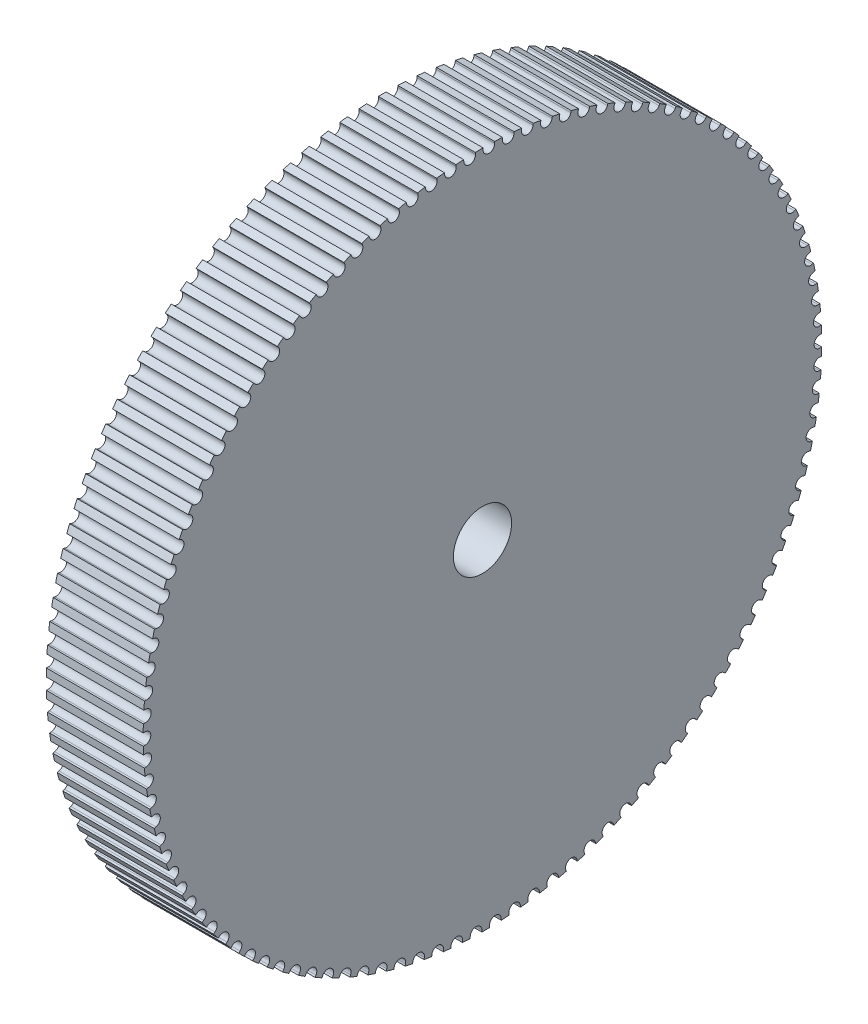
SolidWorks part; units mm, degrees
material "PA Type 6"
ref_plane "Front Plane" through (0, 0, 0) normal (0, 0, 1) x (1, 0, 0)
ref_plane "Top Plane" through (0, 0, 0) normal (0, 1, 0) x (1, 0, 0)
ref_plane "Right Plane" through (0, 0, 0) normal (1, 0, 0) x (0, 0, -1)
sketch "Sketch1" plane through (0, 0, 0) normal (1, 0, 0) x (0, 0, -1)
  circle A0 centre (0, 0) radius 3
  circle A1 centre (0, 0) radius 35
extrude "Boss-Extrude1" add sketch "Sketch1" along normal blind 10
sketch "Sketch2" plane through (10, 0, 0) normal (1, 0, 0) x (0, 0, -1)
  line L0 (0.6612, 35.6936) -> (0.6612, 34.8085) construction
  line L1 (1.2612, 35.6936) -> (1.2612, 34.8085)
  line L2 (0.0612, 35.6936) -> (0.0612, 34.8085)
  arc A0 (1.2612, 35.6936) -> (0.0612, 35.6936) centre (0.6612, 35.6936) ccw
  arc A1 (0.0612, 34.8085) -> (1.2612, 34.8085) centre (0.6612, 34.8085) ccw
  point P2 (0.6612, 35.251)
  point P7 (0.7546, 34.6119)
  point P8 (0.6612, 34.8085)
  dimension "D1" = 0.6
extrude "Cut-Extrude1" cut sketch "Sketch2" against normal blind 10
pattern_circular "CirPattern1" count 110 over 360 about axis through (10, 0, 0) along (1, 0, 0) of "Cut-Extrude1"
